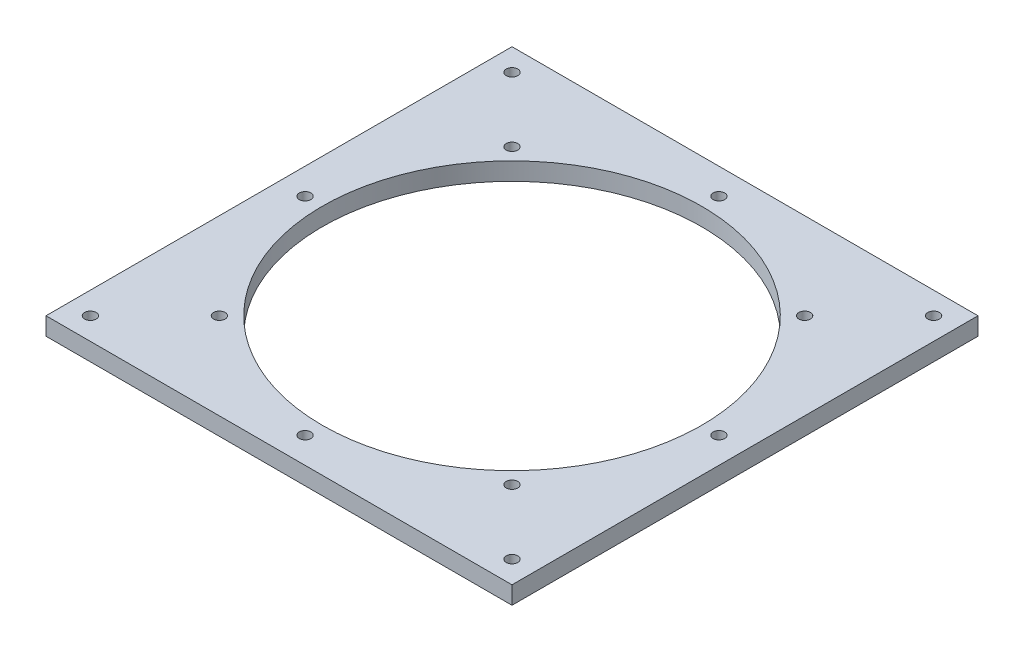
SolidWorks part; units mm, degrees
ref_plane "前视基准面" through (0, 0, 0) normal (0, 0, 1) x (1, 0, 0)
ref_plane "上视基准面" through (0, 0, 0) normal (0, 1, 0) x (1, 0, 0)
ref_plane "右视基准面" through (0, 0, 0) normal (1, 0, 0) x (0, 0, -1)
other "Configuration Table"
sketch "草图1" plane through (0, 0, 0) normal (0, 1, 0) x (1, 0, 0)
  line L0 (0, 101) -> (0, 85.5)
  line L2 (-105, -105) -> (105, -105)
  line L3 (-105, -105) -> (-105, 105)
  line L4 (-105, 105) -> (105, 105)
  line L5 (105, -105) -> (105, 105)
  line L6 (-105, -105) -> (105, 105) construction
  line L7 (-105, 105) -> (105, -105) construction
  circle A0 centre (0, 0) radius 72.5
  circle A1 centre (0, 0) radius 85.5
  circle A2 centre (0, 0) radius 101
  circle A3 centre (0, 93.25) radius 2.6
  circle A4 centre (93.25, 0) radius 2.6
  circle A5 centre (0, -93.25) radius 2.6
  circle A6 centre (-93.25, 0) radius 2.6
  point P19 (0, 0)
  dimension "D1" = 145
  dimension "D3" = 202
  dimension "D4" = 5.2
  dimension "D6" = 210
  dimension "D7" = 210
  dimension "D2" = 13
  dimension "D5" = 4
extrude "凸台-拉伸1" add sketch "草图1" along normal blind 8 contours L2 L5 L4 L3 A2 | A3 A1 A2 A6 A5 A4 region at (69.3978, 0, -69.3978) region at (-102.0302, 0, 0)
sketch "草图2" plane through (0, 8, 0) normal (0, 1, 0) x (1, 0, 0)
  line L0 (-105, 155) -> (-55, 155)
  line L1 (-105, 105) -> (-95, 105)
  line L2 (-105, 105) -> (-105, 95)
  line L3 (-105, 95) -> (-95, 95)
  line L4 (-95, 105) -> (-95, 95)
  line L5 (-105, 105) -> (105, 105)
  line L6 (-105, 105) -> (-105, 155)
  line L7 (-105, 155) -> (105, 155)
  line L8 (105, 105) -> (105, 155)
  circle A0 centre (-95, 95) radius 2.6
  circle A1 centre (0, 93.25) radius 2.6
  circle A2 centre (95, 95) radius 2.6
  circle A3 centre (95, -95) radius 2.6
  circle A4 centre (-95, -95) radius 2.6
  circle A5 centre (65.9377, 65.9377) radius 2.6
  circle A6 centre (93.25, 0) radius 2.6
  circle A7 centre (65.9377, -65.9377) radius 2.6
  circle A8 centre (0, -93.25) radius 2.6
  circle A9 centre (-65.9377, -65.9377) radius 2.6
  circle A10 centre (-93.25, 0) radius 2.6
  circle A11 centre (-65.9377, 65.9377) radius 2.6
  point P17 (0, 0)
  point P33 (0, 0)
  point P34 (0, 0)
  dimension "D3" = 4
  dimension "D4" = 5.2
  dimension "D5" = 8
  dimension "D1" = 10
  dimension "D2" = 10
  dimension "D6" = 50
  dimension "D7" = 50
extrude "切除-拉伸1" cut sketch "草图2" against normal blind 10 contours A7 | A2 | A11 | A5 | A9 | A3 | A4 | A0 region at (95, 8, -95) region at (65.9377, 8, 65.9377)
